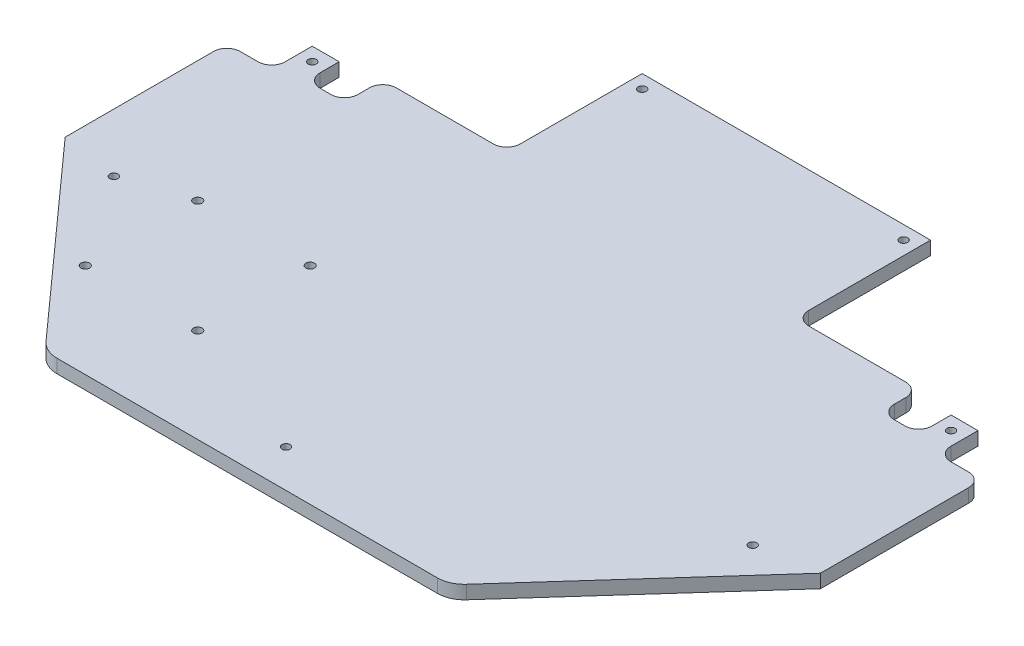
SolidWorks part; units mm, degrees
material "ABS PC"
ref_plane "Plan de face" through (0, 0, 0) normal (0, 0, 1) x (1, 0, 0)
ref_plane "Plan de dessus" through (0, 0, 0) normal (0, 1, 0) x (1, 0, 0)
ref_plane "Plan de droite" through (0, 0, 0) normal (1, 0, 0) x (0, 0, -1)
sketch "Esquisse1" plane through (0, 0, 0) normal (0, 1, 0) x (1, 0, 0)
  line L0 (-101.1, -245.0829) -> (-95, -245.0829) construction
  line L1 (-140.1, 31.2) -> (140.1, 31.2)
  line L2 (-140.1, 31.2) -> (-140.1, -245.0829)
  line L3 (-140.1, -245.0829) -> (140.1, -245.0829)
  line L4 (140.1, 31.2) -> (140.1, -245.0829)
  line L8 (-114.5, 31.2) -> (114.5, 31.2) construction
  line L9 (-140.1, 4) -> (-140.1, -4) construction
  line L10 (140.1, -4) -> (140.1, 4) construction
extrude "Boss.-Extru.1" add sketch "Esquisse1" along normal blind 5
sketch "Esquisse4" plane through (0, 5, 0) normal (0, 1, 0) x (1, 0, 0)
  line L0 (140.1, -245.0829) -> (101.1, -245.0829)
  line L1 (140.1, -245.0829) -> (140.1, -206.0829)
  line L2 (-101.1, -245.0829) -> (-140.1, -245.0829)
  line L3 (-140.1, -245.0829) -> (-140.1, -206.0829)
  arc A1 (101.1, -245.0829) -> (140.1, -206.0829) centre (101.1, -206.0829) ccw
  arc A3 (-140.1, -206.0829) -> (-101.1, -245.0829) centre (-101.1, -206.0829) ccw
  arc A4 (101.1, -245.0829) -> (140.1, -206.0829) centre (101.1, -206.0829) ccw construction
  arc A5 (-140.1, -206.0829) -> (-101.1, -245.0829) centre (-101.1, -206.0829) ccw construction
extrude "Enlèv. mat.-Extru.3" cut sketch "Esquisse4" against normal through all
sketch "Esquisse6" plane through (0, 5, 0) normal (0, 1, 0) x (1, 0, 0)
  line L0 (99.5, 0) -> (99.5, 26.9) construction
  line L1 (140.1, 31.2) -> (53.5, 31.2)
  line L2 (140.1, 31.2) -> (140.1, -41.25)
  line L3 (135.1, -36.25) -> (128.5, -36.25)
  line L4 (99.5, -24) -> (99.5, -28.25)
  line L5 (94.5, -19) -> (58.5, -19)
  line L6 (53.5, -14) -> (53.5, 31.2)
  line L9 (55.5, 15) -> (55.5, -15) construction
  line L10 (88, -16) -> (89, -16) construction
  line L11 (-53.5, -14) -> (-53.5, 31.2)
  line L12 (-94.5, -19) -> (-58.5, -19)
  line L13 (-99.5, -24) -> (-99.5, -28.25)
  line L14 (129.94, -36.25) -> (140.1, -36.25) construction
  line L15 (-135.1, -36.25) -> (-128.5, -36.25)
  line L16 (-140.1, 31.2) -> (-140.1, -41.25)
  line L17 (-140.1, 31.2) -> (-53.5, 31.2)
  line L18 (113.5, -28.25) -> (113.5, -21.2)
  line L19 (113.5, -21.2) -> (123.5, -21.2)
  line L20 (123.5, -21.2) -> (123.5, -31.25)
  line L21 (108.5, -33.25) -> (104.5, -33.25)
  line L22 (-123.5, -21.2) -> (-123.5, -31.25)
  line L23 (-113.5, -21.2) -> (-123.5, -21.2)
  line L24 (-113.5, -28.25) -> (-113.5, -21.2)
  line L25 (0, 0) -> (0, 86.4947) construction
  line L26 (-108.5, -33.25) -> (-104.5, -33.25)
  line L27 (140.1, 36.25) -> (140.1, -245.0829) construction
  arc A0 (140.1, -41.25) -> (135.1, -36.25) centre (135.1, -41.25) ccw
  arc A1 (-99.5, -24) -> (-94.5, -19) centre (-94.5, -24) cw
  arc A2 (58.5, -19) -> (53.5, -14) centre (58.5, -14) cw
  arc A3 (-104.5, -33.25) -> (-99.5, -28.25) centre (-104.5, -28.25) ccw
  arc A4 (104.5, -33.25) -> (99.5, -28.25) centre (104.5, -28.25) cw
  arc A5 (99.5, -24) -> (94.5, -19) centre (94.5, -24) ccw
  arc A6 (-58.5, -19) -> (-53.5, -14) centre (-58.5, -14) ccw
  arc A7 (-140.1, -41.25) -> (-135.1, -36.25) centre (-135.1, -41.25) cw
  arc A8 (113.5, -28.25) -> (108.5, -33.25) centre (108.5, -28.25) cw
  arc A9 (123.5, -31.25) -> (128.5, -36.25) centre (128.5, -31.25) ccw
  arc A10 (-123.5, -31.25) -> (-128.5, -36.25) centre (-128.5, -31.25) cw
  arc A11 (-113.5, -28.25) -> (-108.5, -33.25) centre (-108.5, -28.25) ccw
  point P41 (99.5, -36.25)
  point P43 (99.5, -19)
  point P49 (0, 21.2)
  point P58 (113.5, -33.25)
  dimension "D1" = 5
  dimension "D4" = 3
  dimension "D2" = 2
  dimension "D3" = 3
extrude "Enlèv. mat.-Extru.5" cut sketch "Esquisse6" against normal through all
sketch "Esquisse8" plane through (0, 0, 0) normal (0, -1, 0) x (1, 0, 0)
  line L2 (0, 0) -> (0, -63.4963) construction
  line L4 (53.5, -31.2) -> (53.5, 14) construction
  line L5 (53.5, -31.2) -> (-53.5, -31.2) construction
  line L6 (-53.5, 14) -> (-53.5, -31.2) construction
  circle A0 centre (-48.5, -26.2) radius 1.5
  circle A1 centre (48.5, -26.2) radius 1.5
  dimension "D1" = 3
  dimension "D4" = 5
  dimension "D2" = 3
  dimension "D3" = 5
  dimension "D5" = 5
  dimension "D6" = 5
extrude "Enlèv. mat.-Extru.8" cut sketch "Esquisse8" against normal through all
sketch "Esquisse12" plane through (0, 5, 0) normal (0, 1, 0) x (1, 0, 0)
  line L0 (-140.1, -96.25) -> (-75, -168.8)
  line L3 (-75, -168.8) -> (75, -168.8)
  line L4 (75, -168.8) -> (140.1, -96.25)
  line L5 (140.1, -206.0829) -> (140.1, -41.25) construction
  line L6 (-140.1, -41.25) -> (-140.1, -206.0829) construction
  line L9 (-140.1, -96.25) -> (-140.1, -294.9836)
  line L10 (-140.1, -294.9836) -> (146.0328, -294.9836)
  line L11 (146.0328, -294.9836) -> (140.1, -96.25)
  line L12 (128.5, -36.25) -> (135.1, -36.25) construction
  line L13 (-135.1, -36.25) -> (-128.5, -36.25) construction
  line L14 (53.5, 31.2) -> (-53.5, 31.2) construction
  dimension "D1" = 60
  dimension "D2" = 60
  dimension "D3" = 200
  dimension "D4" = 150
  dimension "D5" = 65.1
extrude "Enlèv. mat.-Extru.15" cut sketch "Esquisse12" against normal through all
fillet "Congé1" radius 10 2 edges at (-75, 2.5, 168.8) (75, 2.5, 168.8)
sketch "Esquisse13" plane through (0, 5, 0) normal (0, 1, 0) x (1, 0, 0)
  line L0 (70.5375, -168.8) -> (-70.5375, -168.8) construction
  circle A0 centre (0.3874, -154.8) radius 1.5
  arc A1 (-77.9803, -165.4786) -> (-70.5375, -168.8) centre (-70.5375, -158.8) ccw construction
  point P9 (-74.6126, -167.932)
  dimension "D2" = 75
  dimension "D3" = 3
  dimension "D1" = 14
extrude "Enlèv. mat.-Extru.16" cut sketch "Esquisse13" against normal through all
sketch "Esquisse14" plane through (0, 5, 0) normal (0, 1, 0) x (1, 0, 0)
  line L0 (70.5375, -168.8) -> (-70.5375, -168.8) construction
  line L2 (-140.1, -41.25) -> (-140.1, -96.25) construction
  circle A0 centre (-95.1, -133.8) radius 1.6
  circle A1 centre (-53.38, -133.8) radius 1.6
  circle A2 centre (-95.1, -92.08) radius 1.6
  circle A3 centre (-53.38, -92.08) radius 1.6
  dimension "D5" = 3.2
  dimension "D6" = 3.2
  dimension "D7" = 3.2
  dimension "D8" = 3.2
  dimension "D9" = 35
  dimension "D11" = 45
  dimension "D10" = 45
  dimension "D1" = 41.72
  dimension "D2" = 41.72
  dimension "D3" = 41.72
  dimension "D4" = 41.72
  dimension "D12" = 35
extrude "Enlèv. mat.-Extru.17" cut sketch "Esquisse14" against normal through all
sketch "Esquisse15" plane through (0, 5, 0) normal (0, 1, 0) x (1, 0, 0)
  line L0 (-123.5, -21.2) -> (-113.5, -21.2) construction
  line L1 (-123.5, -31.25) -> (-123.5, -21.2) construction
  line L2 (0, 31.2) -> (0, -84.5085) construction
  line L3 (53.5, 31.2) -> (-53.5, 31.2) construction
  circle A0 centre (-118.5, -26.2) radius 1.5
  circle A1 centre (118.5, -26.2) radius 1.5
  dimension "D1" = 3
  dimension "D2" = 5
  dimension "D3" = 5
extrude "Enlèv. mat.-Extru.18" cut sketch "Esquisse15" against normal through all
sketch "Esquisse17" plane through (0, 5, 0) normal (0, 1, 0) x (1, 0, 0)
  line L0 (-118.5, -21.2) -> (-118.5, -131.6683) construction
  line L1 (-123.5, -21.2) -> (-113.5, -21.2) construction
  line L2 (0, 31.2) -> (0, -17.0556) construction
  line L3 (53.5, 31.2) -> (-53.5, 31.2) construction
  circle A0 centre (-118.5, -99.8) radius 1.5
  circle A1 centre (-118.5, -26.2) radius 1.5 construction
  circle A2 centre (118.5, -99.8) radius 1.5
  dimension "D1" = 3
  dimension "D2" = 73.6
extrude "Enlèv. mat.-Extru.20" cut sketch "Esquisse17" against normal through all
